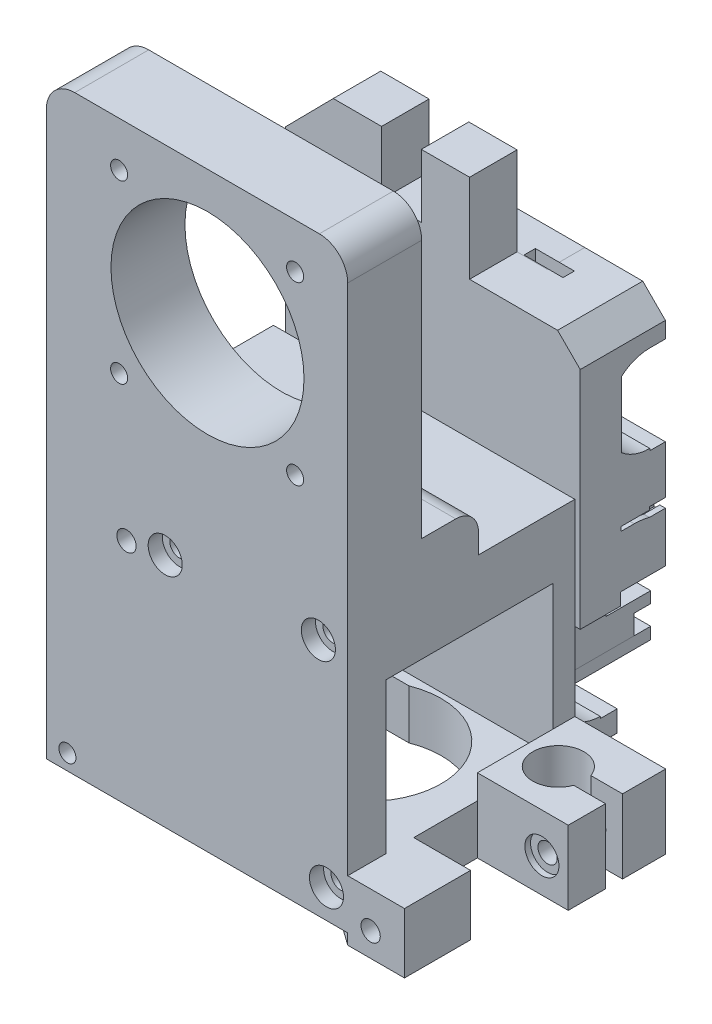
SolidWorks part; units mm, degrees
ref_plane "Front Plane" through (0, 0, 0) normal (0, 0, 1) x (1, 0, 0)
ref_plane "Top Plane" through (0, 0, 0) normal (0, 1, 0) x (1, 0, 0)
ref_plane "Right Plane" through (0, 0, 0) normal (1, 0, 0) x (0, 0, -1)
sketch "Sketch1" plane through (0, 0, 0) normal (0, 0, 1) x (1, 0, 0)
  line L1 (-22.5, 22.5) -> (22.5, 22.5)
  line L2 (-22.5, 22.5) -> (-22.5, -22.5)
  line L3 (-22.5, -22.5) -> (22.5, -22.5)
  line L4 (22.5, 22.5) -> (22.5, -22.5)
  line L5 (-22.5, 22.5) -> (22.5, -22.5) construction
  line L6 (-22.5, -22.5) -> (22.5, 22.5) construction
  point P0 (0, 0)
  dimension "D1" = 45
  dimension "D2" = 45
extrude "Boss-Extrude1" add sketch "Sketch1" along normal blind 35
sketch "Sketch2" plane through (0, 0, 35) normal (0, 0, 1) x (1, 0, 0)
  circle A0 centre (0, 0) radius 13
extrude "Cut-Extrude3" cut sketch "Sketch2" against normal blind 35
sketch "Sketch4" plane through (0, 0, 0) normal (0, 0, -1) x (-1, 0, 0)
  circle A0 centre (-15.8089, 15.9288) radius 1.7
sketch "Sketch5" plane through (0, 0, 0) normal (0, 0, -1) x (-1, 0, 0)
  circle A0 centre (-15.7813, -15.0653) radius 1.7
sketch "Sketch6" plane through (0, 0, 0) normal (0, 0, -1) x (-1, 0, 0)
  circle A0 centre (15.2203, -15.0657) radius 1.7
sketch "Sketch7" plane through (0, 0, 0) normal (0, 0, -1) x (-1, 0, 0)
  circle A0 centre (15.2, 15.9234) radius 1.7
extrude "Cut-Extrude8" cut sketch "Sketch4" against normal blind 35 contours A0
extrude "Cut-Extrude9" cut sketch "Sketch7" against normal blind 35 contours A0
extrude "Cut-Extrude10" cut sketch "Sketch6" against normal blind 35 contours A0
extrude "Cut-Extrude11" cut sketch "Sketch5" against normal blind 35 contours A0
sketch "Sketch8" plane through (22.5, 0, 0) normal (1, 0, 0) x (0, 0, -1)
  line L0 (-4.3639, -12.0361) -> (-35, -12.0361)
  line L2 (-35, -22.5) -> (-35, 22.5) construction
  line L3 (-35, -12.0361) -> (-35, 22.5)
  line L4 (-35, 22.5) -> (-8.4231, 22.5)
  line L5 (-35, 22.5) -> (0, 22.5) construction
  line L6 (-8.4231, 22.5) -> (-8.4231, 12.9255)
  line L7 (-8.4231, 12.9255) -> (-4.3639, 12.9255)
  line L8 (-4.3639, 12.9255) -> (-4.3639, -12.0361)
extrude "Cut-Extrude12" cut sketch "Sketch8" against normal blind 12
sketch "Sketch14" plane through (0, 22.5, 0) normal (0, 1, 0) x (1, 0, 0)
  line L1 (3.1909, -14.7293) -> (9.1909, -14.7293)
  line L2 (3.1909, -14.7293) -> (3.1909, -20.7293)
  line L3 (3.1909, -20.7293) -> (9.1909, -20.7293)
  line L4 (9.1909, -14.7293) -> (9.1909, -20.7293)
  line L5 (3.1909, -14.7293) -> (9.1909, -20.7293) construction
  line L6 (3.1909, -20.7293) -> (9.1909, -14.7293) construction
  point P0 (6.1909, -17.7293)
  point P5 (0, 0)
extrude "Boss-Extrude4" add sketch "Sketch14" along normal blind 2 and the other way blind 37.5
sketch "Sketch20" plane through (0, 24.5, 0) normal (0, 1, 0) x (1, 0, 0)
  line L0 (3.1909, -20.7293) -> (9.1909, -14.7293) construction
  circle A0 centre (6.1909, -17.7293) radius 2.2
  dimension "D1" = 4.4
extrude "Cut-Extrude17" cut sketch "Sketch20" against normal blind 7 and the other way through all contours A0
sketch "Sketch21" plane through (0, 17.5, 0) normal (0, 1, 0) x (1, 0, 0)
  circle A0 centre (6.1909, -17.7293) radius 1.75
extrude "Cut-Extrude18" cut sketch "Sketch21" against normal blind 2
ref_plane "Plane6" through (0, 16.5, 0) normal (0, 1, 0) x (1, 0, 0)
mirror "Mirror6" about plane through (0, 16.5, 0) normal (0, 1, 0) of "Cut-Extrude17"
sketch "Sketch22" plane through (0, -22.5, 0) normal (0, -1, 0) x (1, 0, 0)
  line L1 (-28.0826, 40.0025) -> (25, 40.0025)
  line L2 (-28.0826, 40.0025) -> (-28.0826, 0)
  line L3 (-28.0826, 0) -> (25, 0)
  line L4 (25, 40.0025) -> (25, 0)
  line L5 (-28.0826, 40.0025) -> (25, 0) construction
  line L6 (-28.0826, 0) -> (25, 40.0025) construction
  point P0 (-1.5413, 20.0013)
extrude "Boss-Extrude5" add sketch "Sketch22" along normal blind 44.5712 and the other way blind 1.5626
sketch "Sketch23" plane through (-28.0826, 0, 0) normal (-1, 0, 0) x (0, 0, 1)
  line L1 (3.8043, -58.359) -> (33.254, -58.359)
  line L2 (3.8043, -58.359) -> (3.8043, -31.8415)
  line L3 (3.8043, -31.8415) -> (33.254, -31.8415)
  line L4 (33.254, -58.359) -> (33.254, -31.8415)
  line L5 (3.8043, -58.359) -> (33.254, -31.8415) construction
  line L6 (3.8043, -31.8415) -> (33.254, -58.359) construction
  point P0 (18.5291, -45.1003)
extrude "Cut-Extrude19" cut sketch "Sketch23" against normal through all
sketch "Sketch25" plane through (0, -20.9374, 0) normal (0, 1, 0) x (1, 0, 0)
  circle A0 centre (6.1909, -17.7293) radius 5
extrude "Cut-Extrude24" cut sketch "Sketch25" against normal blind 2.6
sketch "Sketch26" plane through (0, -23.5374, 0) normal (0, 1, 0) x (1, 0, 0)
  circle A0 centre (6.1909, -17.7293) radius 8.1
extrude "Cut-Extrude25" cut sketch "Sketch26" against normal blind 4 contours A0
sketch "Sketch27" plane through (0, -27.5374, 0) normal (0, 1, 0) x (1, 0, 0)
  circle A0 centre (6.1909, -17.7293) radius 6.7
extrude "Cut-Extrude28" cut sketch "Sketch27" against normal blind 6
sketch "Sketch30" plane through (0, -58.359, 0) normal (0, 1, 0) x (1, 0, 0)
  circle A0 centre (6.2079, -17.7293) radius 13
extrude "Cut-Extrude30" cut sketch "Sketch30" against normal blind 10.7676
sketch "Sketch31" plane through (0, -67.0712, 0) normal (0, -1, 0) x (1, 0, 0)
  line L1 (-17.2669, 29.2843) -> (2.0826, 29.2843)
  line L2 (-17.2669, 29.2843) -> (-17.2669, 5.6402)
  line L3 (-17.2669, 5.6402) -> (2.0826, 5.6402)
  line L4 (2.0826, 29.2843) -> (2.0826, 5.6402)
  line L5 (-17.2669, 29.2843) -> (2.0826, 5.6402) construction
  line L6 (-17.2669, 5.6402) -> (2.0826, 29.2843) construction
  point P0 (-7.5922, 17.4622)
extrude "Cut-Extrude31" cut sketch "Sketch31" against normal blind 9.6643
sketch "Sketch34" plane through (-28.0826, 0, 0) normal (-1, 0, 0) x (0, 0, 1)
  circle A4 centre (35.5309, -28.495) radius 1.5
  circle A5 centre (3.5309, -28.495) radius 1.5
  circle A6 centre (35.5309, -60.495) radius 1.5
  circle A7 centre (3.5309, -60.495) radius 1.5
extrude "Cut-Extrude32" cut sketch "Sketch34" against normal blind 9 contours A5 | A7 | A6 | A4
sketch "Sketch37" plane through (25, 0, 0) normal (1, 0, 0) x (0, 0, -1)
  line L1 (-28.3675, -68.9589) -> (-40.0025, -68.9589)
  line L2 (-28.3675, -68.9589) -> (-28.3675, -58.359)
  line L3 (-28.3675, -58.359) -> (-40.0025, -58.359)
  line L4 (-40.0025, -68.9589) -> (-40.0025, -58.359)
  line L5 (-28.3675, -68.9589) -> (-40.0025, -58.359) construction
  line L6 (-28.3675, -58.359) -> (-40.0025, -68.9589) construction
  point P0 (-34.185, -63.659)
extrude "Boss-Extrude6" add sketch "Sketch37" along normal blind 10 and the other way blind 5 draft 29
sketch "Sketch38" plane through (0, 0, 40.0025) normal (0, 0, 1) x (1, 0, 0)
  circle A0 centre (29.0349, -64.7484) radius 1.7
extrude "Cut-Extrude33" cut sketch "Sketch38" against normal blind 10 contours A0
sketch "Sketch39" plane through (0, 0, 40.0025) normal (0, 0, 1) x (1, 0, 0)
  circle A0 centre (-13.9651, -26.7484) radius 1.7
extrude "Cut-Extrude34" cut sketch "Sketch39" against normal through all contours A0
sketch "Sketch40" plane through (25, 0, 0) normal (1, 0, 0) x (0, 0, -1)
  line L0 (0, -67.0712) -> (-28.3675, -67.0712) construction
  line L1 (-17.1599, -54.0712) -> (0, -54.0712)
  line L2 (-17.1599, -54.0712) -> (-17.1599, -67.0712)
  line L3 (-17.1599, -67.0712) -> (0, -67.0712)
  line L4 (0, -54.0712) -> (0, -67.0712)
  line L5 (-17.1599, -54.0712) -> (0, -67.0712) construction
  line L6 (-17.1599, -67.0712) -> (0, -54.0712) construction
  point P0 (-8.5799, -60.5712)
extrude "Boss-Extrude7" add sketch "Sketch40" along normal blind 16 contours L2 L3 L4 L1
sketch "Sketch41" plane through (0, -54.0712, 1.2693) normal (0, 1, 0) x (1, 0, 0)
  circle A0 centre (31.1639, -7.7934) radius 4.5
extrude "Cut-Extrude35" cut sketch "Sketch41" against normal blind 15 contours A0
sketch "Sketch42" plane through (0, -54.0712, 0) normal (0, 1, 0) x (1, 0, 0)
  line L1 (33.5282, -7.5957) -> (42.8596, -7.5957)
  line L2 (33.5282, -7.5957) -> (33.5282, -10.5957)
  line L3 (33.5282, -10.5957) -> (42.8596, -10.5957)
  line L4 (42.8596, -7.5957) -> (42.8596, -10.5957)
  line L5 (33.5282, -7.5957) -> (42.8596, -10.5957) construction
  line L6 (33.5282, -10.5957) -> (42.8596, -7.5957) construction
  point P0 (38.1939, -9.0957)
extrude "Cut-Extrude36" cut sketch "Sketch42" against normal blind 15
sketch "Sketch43" plane through (0, 0, 0) normal (0, 0, -1) x (-1, 0, 0)
  line L1 (-34.6289, -64.4039) -> (-32.7385, -61.0954)
  line L2 (-32.7385, -61.0954) -> (-34.6585, -57.804)
  line L3 (-34.6585, -57.804) -> (-38.4689, -57.821)
  line L4 (-38.4689, -57.821) -> (-40.3594, -61.1295)
  line L5 (-40.3594, -61.1295) -> (-38.4394, -64.421)
  line L6 (-38.4394, -64.421) -> (-34.6289, -64.4039)
  circle A1 centre (-36.5489, -61.1125) radius 3.3 construction
extrude "Cut-Extrude37" cut sketch "Sketch43" against normal blind 5
sketch "Sketch44" plane through (0, 0, 17.1599) normal (0, 0, 1) x (1, 0, 0)
  circle A0 centre (36.3605, -61.0871) radius 1.7
extrude "Cut-Extrude38" cut sketch "Sketch44" against normal blind 23 contours A0
sketch "Sketch48" plane through (0, 0, 0) normal (0, 0, -1) x (-1, 0, 0)
  line L1 (9.0667, -28.8111) -> (10.9572, -25.5026)
  line L2 (10.9572, -25.5026) -> (9.0372, -22.2111)
  line L3 (9.0372, -22.2111) -> (5.2267, -22.2282)
  line L4 (5.2267, -22.2282) -> (3.3362, -25.5367)
  line L5 (3.3362, -25.5367) -> (5.2563, -28.8281)
  line L6 (5.2563, -28.8281) -> (9.0667, -28.8111)
  circle A1 centre (7.1467, -25.5196) radius 3.3 construction
sketch "Sketch49" plane through (0, 0, 0) normal (0, 0, -1) x (-1, 0, 0)
  line L1 (-19.3395, -65.2659) -> (-17.449, -61.9575)
  line L2 (-17.449, -61.9575) -> (-19.369, -58.666)
  line L3 (-19.369, -58.666) -> (-23.1795, -58.6831)
  line L4 (-23.1795, -58.6831) -> (-25.07, -61.9916)
  line L5 (-25.07, -61.9916) -> (-23.15, -65.283)
  line L6 (-23.15, -65.283) -> (-19.3395, -65.2659)
  circle A1 centre (-21.2595, -61.9745) radius 3.3 construction
sketch "Sketch50" plane through (0, 0, 0) normal (0, 0, -1) x (-1, 0, 0)
  line L1 (-17.9116, -28.2435) -> (-16.0212, -24.935)
  line L2 (-16.0212, -24.935) -> (-17.9412, -21.6436)
  line L3 (-17.9412, -21.6436) -> (-21.7517, -21.6606)
  line L4 (-21.7517, -21.6606) -> (-23.6421, -24.9691)
  line L5 (-23.6421, -24.9691) -> (-21.7221, -28.2606)
  line L6 (-21.7221, -28.2606) -> (-17.9116, -28.2435)
  circle A1 centre (-19.8316, -24.9521) radius 3.3 construction
sketch "Sketch51" plane through (0, 0, 40.0025) normal (0, 0, 1) x (1, 0, 0)
  circle A0 centre (-7.1467, -25.5196) radius 1.7
sketch "Sketch52" plane through (0, 0, 40.0025) normal (0, 0, 1) x (1, 0, 0)
  circle A0 centre (19.8316, -24.9521) radius 1.7
sketch "Sketch53" plane through (0, 0, 40.0025) normal (0, 0, 1) x (1, 0, 0)
  circle A0 centre (21.2595, -61.9745) radius 1.7
extrude "Cut-Extrude39" cut sketch "Sketch48" against normal blind 5
extrude "Cut-Extrude40" cut sketch "Sketch49" against normal blind 5
extrude "Cut-Extrude41" cut sketch "Sketch50" against normal blind 5
extrude "Cut-Extrude42" cut sketch "Sketch53" against normal through all contours A0
extrude "Cut-Extrude43" cut sketch "Sketch52" against normal through all contours A0
extrude "Cut-Extrude44" cut sketch "Sketch51" against normal through all
sketch "Sketch55" plane through (0, 0, 0) normal (0, 0, -1) x (-1, 0, 0)
  line L1 (16.7453, -30.1645) -> (18.3136, -26.0487)
  line L2 (18.3136, -26.0487) -> (15.5334, -22.6326)
  line L3 (15.5334, -22.6326) -> (11.1849, -23.3323)
  line L4 (11.1849, -23.3323) -> (9.6166, -27.448)
  line L5 (9.6166, -27.448) -> (12.3967, -30.8642)
  line L6 (12.3967, -30.8642) -> (16.7453, -30.1645)
  circle A0 centre (13.9651, -26.7484) radius 3.8144 construction
extrude "Cut-Extrude46" cut sketch "Sketch55" against normal blind 5
sketch "Sketch57" plane through (0, 0, 40.0025) normal (0, 0, 1) x (1, 0, 0)
  circle A0 centre (-7.1467, -25.5196) radius 3
sketch "Sketch58" plane through (0, 0, 40.0025) normal (0, 0, 1) x (1, 0, 0)
  circle A0 centre (19.8316, -24.9521) radius 3
sketch "Sketch59" plane through (0, 0, 40.0025) normal (0, 0, 1) x (1, 0, 0)
  circle A0 centre (21.2595, -61.9745) radius 3
extrude "Cut-Extrude48" cut sketch "Sketch57" against normal blind 2.5
extrude "Cut-Extrude49" cut sketch "Sketch58" against normal blind 2.5 contours A0
extrude "Cut-Extrude50" cut sketch "Sketch59" against normal blind 2.5 contours A0
sketch "Sketch60" plane through (0, 0, 0) normal (0, 0, -1) x (-1, 0, 0)
  circle A0 centre (-15.8089, 15.9288) radius 3
  circle A1 centre (15.2, 15.9234) radius 3
  circle A2 centre (-15.7813, -15.0653) radius 3
  circle A3 centre (15.2203, -15.0657) radius 3
extrude "Cut-Extrude51" cut sketch "Sketch60" against normal blind 1
sketch "Sketch61" plane through (9.1909, 0, 0) normal (1, 0, 0) x (0, 0, -1)
  line L1 (-21.0836, 7.2178) -> (-14.5415, 7.2178)
  line L2 (-21.0836, 7.2178) -> (-21.0836, -6.8125)
  line L3 (-21.0836, -6.8125) -> (-14.5415, -6.8125)
  line L4 (-14.5415, 7.2178) -> (-14.5415, -6.8125)
  line L5 (-21.0836, 7.2178) -> (-14.5415, -6.8125) construction
  line L6 (-21.0836, -6.8125) -> (-14.5415, 7.2178) construction
  point P0 (-17.8126, 0.2026)
extrude "Cut-Extrude52" cut sketch "Sketch61" against normal blind 6.5 contours L3 L4 L1 L2
sketch "Sketch62" plane through (-22.5, 0, 0) normal (-1, 0, 0) x (0, 0, 1)
  circle A0 centre (9.4038, -7.1271) radius 1.7
sketch "Sketch63" plane through (-22.5, 0, 0) normal (-1, 0, 0) x (0, 0, 1)
  circle A0 centre (29.5162, -7.0688) radius 1.7
sketch "Sketch67" plane through (-22.5, -2.4684, 0) normal (-1, 0, 0) x (0, 0, 1)
  line L1 (26.7141, -1.4425) -> (32.3183, -1.4425)
  line L2 (26.7141, -1.4425) -> (26.7141, -10.4391)
  line L3 (26.7141, -10.4391) -> (32.3183, -10.4391)
  line L4 (32.3183, -1.4425) -> (32.3183, -10.4391)
  line L5 (26.7141, -1.4425) -> (32.3183, -10.4391) construction
  line L6 (26.7141, -10.4391) -> (32.3183, -1.4425) construction
  point P0 (29.5162, -5.9408)
extrude "Boss-Extrude8" add sketch "Sketch67" against normal blind 33
sketch "Sketch68" plane through (-22.5, -2.4684, 0) normal (-1, 0, 0) x (0, 0, 1)
  line L1 (6.6705, -1.2663) -> (12.2748, -1.2663)
  line L2 (6.6705, -1.2663) -> (6.6705, -10.6664)
  line L3 (6.6705, -10.6664) -> (12.2748, -10.6664)
  line L4 (12.2748, -1.2663) -> (12.2748, -10.6664)
  line L5 (6.6705, -1.2663) -> (12.2748, -10.6664) construction
  line L6 (6.6705, -10.6664) -> (12.2748, -1.2663) construction
  point P0 (9.4726, -5.9663)
extrude "Boss-Extrude9" add sketch "Sketch68" against normal blind 33
extrude "Cut-Extrude55" cut sketch "Sketch63" against normal through all contours A0
extrude "Cut-Extrude56" cut sketch "Sketch62" against normal through all contours A0
sketch "Sketch69" plane through (-22.5, 0, 0) normal (-1, 0, 0) x (0, 0, 1)
  circle A0 centre (9.4038, -7.1271) radius 3
  circle A1 centre (29.5162, -7.0688) radius 3
extrude "Cut-Extrude57" cut sketch "Sketch69" against normal blind 2.5
sketch "Sketch70" plane through (0, 0, 28.3675) normal (0, 0, -1) x (-1, 0, 0)
  line L1 (-25.0573, -66.8115) -> (-25.2594, -62.3352)
  line L2 (-25.2594, -62.3352) -> (-29.2371, -60.2722)
  line L3 (-29.2371, -60.2722) -> (-33.0125, -62.6853)
  line L4 (-33.0125, -62.6853) -> (-32.8104, -67.1616)
  line L5 (-32.8104, -67.1616) -> (-28.8328, -69.2246)
  line L6 (-28.8328, -69.2246) -> (-25.0573, -66.8115)
  circle A0 centre (-29.0349, -64.7484) radius 3.8805 construction
extrude "Cut-Extrude58" cut sketch "Sketch70" against normal blind 2.5
sketch "Sketch71" plane through (0, 0, 17.1599) normal (0, 0, 1) x (1, 0, 0)
  circle A0 centre (36.3605, -61.0871) radius 3
extrude "Cut-Extrude59" cut sketch "Sketch71" against normal blind 1 contours A0
sketch "Sketch73" plane through (0, 0, 40.0025) normal (0, 0, 1) x (1, 0, 0)
  circle A0 centre (-24.3693, -64.3228) radius 1.5
extrude "Cut-Extrude61" cut sketch "Sketch73" against normal blind 5
ref_plane "Plane7" through (0, 0, 17.7293) normal (0, 0, 1) x (1, 0, 0)
ref_plane "Plane8" through (0, -20.9374, 0) normal (0, 1, 0) x (1, 0, 0)
sketch "Sketch78" plane through (0, 0, 17.7293) normal (0, 0, 1) x (1, 0, 0)
  line L0 (25, -20.9374) -> (-28.0826, -20.9374) construction
  line L1 (-33.1226, -20.9374) -> (49.9762, -20.9374)
  line L2 (-33.1226, -20.9374) -> (-33.1226, -72.7681)
  line L3 (-33.1226, -72.7681) -> (49.9762, -72.7681)
  line L4 (49.9762, -20.9374) -> (49.9762, -72.7681)
sketch "Sketch79" plane through (0, -20.9374, 0) normal (0, 1, 0) x (1, 0, 0)
  line L1 (-52.1, -49.3859) -> (43.5589, -49.3859)
  line L2 (-52.1, -49.3859) -> (-52.1, 1.9049)
  line L3 (-52.1, 1.9049) -> (43.5589, 1.9049)
  line L4 (43.5589, -49.3859) -> (43.5589, 1.9049)
extrude "Cut-Extrude62" cut sketch "Sketch79" along normal blind 59 contours L1 L4 L3 L2
sketch "Sketch80" plane through (0, -20.9374, 0) normal (0, 1, 0) x (1, 0, 0)
  line L1 (25, -40.0025) -> (-28.0826, -40.0025)
  line L2 (25, -40.0025) -> (25, -26.9707)
  line L3 (25, -26.9707) -> (-28.0826, -26.9707)
  line L4 (-28.0826, -40.0025) -> (-28.0826, -26.9707)
  line L5 (25, -40.0025) -> (-28.0826, -26.9707) construction
  line L6 (25, -26.9707) -> (-28.0826, -40.0025) construction
  line L7 (25, 0) -> (25, -40.0025) construction
  line L8 (-28.0826, -40.0025) -> (-28.0826, 0) construction
  line L9 (25, -40.0025) -> (-28.0826, -40.0025) construction
  point P0 (-1.5413, -33.4866)
extrude "Boss-Extrude10" add sketch "Sketch80" along normal blind 58
fillet "Fillet1" radius 5 2 edges at (-28.0826, 37.0626, 33.4866) (25, 37.0626, 33.4866)
sketch "Sketch84" plane through (0, 0, 26.9707) normal (0, 0, -1) x (-1, 0, 0)
  circle A0 centre (-0.299, 13.6036) radius 17
extrude "Cut-Extrude63" cut sketch "Sketch84" against normal blind 22
sketch "Sketch85" plane through (0, 0, 40.0025) normal (0, 0, 1) x (1, 0, 0)
  circle A0 centre (15.7368, 29.1356) radius 1.5
  circle A1 centre (15.7368, -1.8644) radius 1.5
  circle A2 centre (-15.2632, -1.8644) radius 1.5
  circle A3 centre (-15.2632, 29.1356) radius 1.5
extrude "Cut-Extrude64" cut sketch "Sketch85" against normal blind 15
sketch "Sketch86" plane through (0, -20.9374, 0) normal (0, 1, 0) x (1, 0, 0)
  line L0 (25, -26.9707) -> (-28.0826, -26.9707) construction
  line L1 (-28.0826, -26.9707) -> (-14.3865, -26.9707)
  line L2 (-28.0826, -26.9707) -> (-28.0826, -16.9707)
  line L3 (-28.0826, -16.9707) -> (-14.3865, -16.9707)
  line L4 (-14.3865, -26.9707) -> (-14.3865, -16.9707)
extrude "Boss-Extrude11" add sketch "Sketch86" along normal blind 7.5
fillet "Fillet3" radius 3 1 edges at (-21.2346, -13.4374, 16.9707)
sketch "Sketch87" plane through (0, -20.9374, 0) normal (0, 1, 0) x (1, 0, 0)
  line L0 (25, -26.9707) -> (-14.3865, -26.9707) construction
  line L1 (25, -16.9707) -> (14.2343, -16.9707)
  line L2 (25, -16.9707) -> (25, -26.9707)
  line L3 (25, -26.9707) -> (14.2343, -26.9707)
  line L4 (14.2343, -16.9707) -> (14.2343, -26.9707)
  line L5 (-14.3865, -16.9707) -> (-28.0826, -16.9707) construction
  line L6 (25, 0) -> (25, -26.9707) construction
extrude "Boss-Extrude12" add sketch "Sketch87" along normal blind 7.5
sketch "Sketch89" plane through (0, -20.9374, 0) normal (0, 1, 0) x (1, 0, 0)
  line L1 (61.8406, -52.5891) -> (-70.6943, -52.5891)
  line L2 (61.8406, -52.5891) -> (61.8406, 20.0544)
  line L3 (61.8406, 20.0544) -> (-70.6943, 20.0544)
  line L4 (-70.6943, -52.5891) -> (-70.6943, 20.0544)
fillet "Fillet6" radius 4 1 edges at (19.6171, -13.4374, 16.9707)
sketch "Sketch90" plane through (0, 0, 0) normal (0, 0, -1) x (-1, 0, 0)
  line L0 (17.0373, -68.362) -> (17.0373, -50.6891)
  line L1 (14.2497, -71.1901) -> (-14.1775, -71.1901)
  line L2 (25.9937, -36.474) -> (25.9937, 10.3734)
  line L4 (-25.9551, -36.6603) -> (-25.9551, -0.6679)
  line L5 (17.0373, -50.6891) -> (26.0173, -50.6891)
  line L6 (-17.4627, -50.6803) -> (-17.4627, -67.8636)
  line L7 (-17.4627, -50.6803) -> (-23.3678, -50.6803)
  line L8 (-17.4627, -67.8636) -> (-14.1775, -71.1901)
  line L9 (17.0373, -68.362) -> (14.2497, -71.1901)
  line L10 (-23.3678, -50.6803) -> (-23.3627, -48.6193)
  line L11 (-23.3627, -43.1803) -> (-23.3627, -48.6193)
  line L13 (26.0173, -50.6891) -> (26.0173, -40.6819)
  line L14 (26.0173, -40.6819) -> (25.9937, -36.474)
  line L15 (-25.9551, -0.6679) -> (-21.9627, 3.3244)
  line L16 (-21.9627, 3.3244) -> (-6.4627, 3.3557)
  line L17 (-6.4627, 3.3557) -> (-6.4627, 18.9227)
  line L18 (-23.3627, -43.1803) -> (-23.3627, -40.3081)
  line L19 (17.549, 18.9227) -> (25.9937, 10.3734)
  line L20 (2.0414, 18.9227) -> (2.0108, 7.7806)
  line L21 (9.0396, 7.7806) -> (9.0396, 18.9227)
  line L22 (2.0108, 7.7806) -> (9.0396, 7.7806)
  line L23 (2.0414, 18.9227) -> (-6.4627, 18.9227)
  line L24 (9.0396, 18.9227) -> (17.549, 18.9227)
  line L25 (-25.9551, -36.6603) -> (-25.9551, -40.3081)
  line L26 (-25.9551, -40.3081) -> (-23.3627, -40.3081)
extrude "Boss-Extrude13" add sketch "Sketch90" along normal blind 15
ref_plane "Plane9" through (24.9551, 0, 0) normal (1, 0, 0) x (0, 0, -1)
sketch "Sketch93" plane through (24.9551, 0, 0) normal (1, 0, 0) x (0, 0, -1)
  circle A0 centre (12.2562, -11.1714) radius 7.6272
  point P2 (12.3899, -11.1491)
  point P3 (12.2562, -11.1714)
extrude "Cut-Extrude66" cut sketch "Sketch93" against normal blind 49.5
sketch "Sketch94" plane through (25.9551, 0, 0) normal (1, 0, 0) x (0, 0, -1)
  line L0 (7.3045, -5.318) -> (7.3045, -17.0156)
  line L1 (12.2545, -3.5044) -> (16.3704, -3.5044)
  line L2 (16.3704, -4.7037) -> (16.3704, -3.5044)
  line L3 (12.2545, -18.8291) -> (12.2475, -19.1753)
  line L4 (12.2475, -19.1753) -> (15.2475, -19.1908)
  line L5 (15.2475, -19.1908) -> (15.2475, -18.2204)
  arc A0 (7.3045, -17.0156) -> (12.2545, -18.8291) centre (12.2545, -11.1668) ccw
  arc A1 (12.2545, -3.5044) -> (7.3045, -5.318) centre (12.2545, -11.1668) ccw
  arc A2 (15.2475, -18.2204) -> (16.3704, -4.7037) centre (12.2545, -11.1668) ccw
extrude "Cut-Extrude67" cut sketch "Sketch94" against normal blind 53.5
ref_plane "Plane10" through (12.4627, 0, 0) normal (1, 0, 0) x (0, 0, -1)
sketch "Sketch95" plane through (12.4627, 0, 0) normal (1, 0, 0) x (0, 0, -1)
  circle A0 centre (12.0924, -56.1751) radius 7.6764
  point P2 (12.8802, -56.0146)
  point P3 (12.4047, -56.2159)
  point P4 (12.8001, -56.3056)
  point P5 (12.4856, -56.2898)
  point P6 (11.8974, -56.2772)
  point P7 (12.0924, -56.1751)
extrude "Cut-Extrude68" cut sketch "Sketch95" against normal blind 25.2
sketch "Sketch96" plane through (17.4627, 0, 0) normal (1, 0, 0) x (0, 0, -1)
  line L0 (7.0266, -61.9445) -> (7.0939, -50.6803)
  line L1 (7.0939, -50.6803) -> (18.0396, -50.6803)
  line L3 (12.0174, -63.8278) -> (12.0174, -64.1642)
  line L4 (12.0174, -64.1642) -> (15, -64.1642)
  line L5 (15, -50.6803) -> (15, -67.8636) construction
  line L6 (15, -64.1642) -> (15, -63.2948)
  arc A0 (7.0266, -61.9445) -> (12.0174, -63.8278) centre (12.1456, -55.9335) ccw
  arc A1 (15, -63.2948) -> (18.0396, -50.6803) centre (12.1456, -55.9335) ccw
  point P6 (15, -63.2948)
extrude "Cut-Extrude69" cut sketch "Sketch96" against normal blind 34.5
sketch "Sketch98" plane through (23.3627, 0, 0) normal (1, 0, 0) x (0, 0, -1)
  line L1 (7.1104, -43.1905) -> (15.1235, -43.1905)
  line L2 (7.1104, -43.1905) -> (7.1104, -38.1356)
  line L3 (7.1104, -38.1356) -> (15.1235, -38.1356)
  line L4 (15.1235, -43.1905) -> (15.1235, -38.1356)
  point P4 (7.1558, -36.6135)
  point P5 (7.1104, -38.1356)
  point P6 (15.1235, -43.1905)
extrude "Cut-Extrude70" cut sketch "Sketch98" against normal through all both and the other way through all
sketch "Sketch99" plane through (23.3627, 0, 0) normal (1, 0, 0) x (0, 0, -1)
  line L1 (15, -48.6193) -> (12.1018, -48.6193)
  line L2 (15, -48.6193) -> (15, -45.1749)
  line L3 (15, -45.1749) -> (12.1018, -45.1749)
  line L4 (12.1018, -48.6193) -> (12.1018, -45.1749)
extrude "Cut-Extrude71" cut sketch "Sketch99" against normal blind 49.5
sketch "Sketch100" plane through (0, 0, -15) normal (0, 0, -1) x (-1, 0, 0)
  line L0 (-25.9551, -28.9452) -> (-24.9628, -28.9452)
  line L1 (-25.9551, -19.1895) -> (-25.9551, -38.1356) construction
  line L2 (-24.9628, -28.9452) -> (-24.9628, -29.6536)
  line L3 (-24.9628, -29.6536) -> (-23.9626, -29.6536)
  line L4 (-23.9626, -29.6536) -> (-23.9626, -28.9452)
  line L5 (-23.9626, -28.9452) -> (-22.9642, -28.9452)
  line L6 (-22.9642, -28.9452) -> (-22.9586, -29.6536)
  line L7 (-22.9586, -29.6536) -> (-21.963, -29.6536)
  line L8 (-21.963, -29.6536) -> (-21.963, -28.9452)
  line L9 (-21.963, -28.9452) -> (-20.9649, -28.9452)
  line L10 (-20.9649, -28.9452) -> (-20.9593, -29.6526)
  line L11 (-20.9593, -29.6526) -> (-19.966, -29.6447)
  line L12 (-19.966, -29.6447) -> (-19.9723, -28.852)
  line L13 (-19.9723, -28.852) -> (-19.3112, -28.5436)
  line L14 (-19.3112, -28.5436) -> (-19.0086, -29.1925)
  line L15 (-19.0086, -29.1925) -> (-18.1014, -28.7694)
  line L16 (-18.1014, -28.7694) -> (-18.4041, -28.1205)
  line L17 (-18.4041, -28.1205) -> (-17.5043, -27.7008)
  line L18 (-17.5043, -27.7008) -> (-17.2016, -28.3497)
  line L19 (-17.2016, -28.3497) -> (-16.2902, -27.9246)
  line L20 (-16.2902, -27.9246) -> (-16.5928, -27.2757)
  line L21 (-16.5928, -27.2757) -> (-15.6945, -26.8567)
  line L22 (-15.6945, -26.8567) -> (-15.2198, -27.8743)
  line L23 (-15.2198, -27.8743) -> (-14.3102, -27.4501)
  line L24 (-14.3102, -27.4501) -> (-14.7283, -26.5536)
  line L25 (-14.7283, -26.5536) -> (-13.7535, -26.5536)
  line L26 (-13.7535, -26.5536) -> (-13.7535, -27.2739)
  line L27 (-13.7535, -27.2739) -> (-12.7588, -27.2739)
  line L28 (-12.7588, -27.2739) -> (-12.7588, -26.5536)
  line L29 (-12.7588, -26.5536) -> (-11.7545, -26.5536)
  line L30 (-11.7545, -26.5536) -> (-11.7545, -27.2739)
  line L31 (-11.7545, -27.2739) -> (-10.7569, -27.2739)
  line L32 (-10.7569, -27.2739) -> (-10.7569, -26.5536)
  line L33 (-10.7569, -26.5536) -> (-9.7531, -26.5536)
  line L34 (-9.7531, -26.5536) -> (-9.7531, -27.2739)
  line L35 (-9.7531, -27.2739) -> (-8.7561, -27.2739)
  line L36 (-8.7561, -27.2739) -> (-8.7561, -26.5536)
  line L37 (-8.7561, -26.5536) -> (-7.7518, -26.5536)
  line L38 (-7.7518, -26.5536) -> (-7.7518, -27.2739)
  line L39 (-7.7518, -27.2739) -> (-7.4588, -27.2739)
  line L40 (-7.4588, -27.2739) -> (-6.7129, -27.7765)
  line L41 (-6.7129, -27.7765) -> (-6.455, -27.9003)
  line L42 (-6.455, -27.9003) -> (-6.8083, -25.7675)
  line L43 (-6.8083, -25.7675) -> (-15.08, -25.7675)
  line L44 (-15.08, -25.7675) -> (-20.1972, -28.16)
  line L45 (-20.1972, -28.16) -> (-25.9551, -28.1993)
  line L46 (-25.9551, -28.1993) -> (-25.9551, -28.9452)
  point P26 (-15.08, -25.7675)
sketch "Sketch104" plane through (0, 0, -15) normal (0, 0, -1) x (-1, 0, 0)
  line L0 (-25.9627, -29.3147) -> (-24.9628, -29.3147)
  line L1 (-24.9628, -28.9452) -> (-24.9628, -29.6536) construction
  line L2 (-24.9628, -29.3147) -> (-24.9627, -30.0666)
  line L3 (-24.9627, -30.0666) -> (-23.9627, -30.0666)
  line L4 (-23.9627, -30.0666) -> (-23.9626, -29.2994)
  line L5 (-23.9626, -29.6536) -> (-23.9626, -28.9452) construction
  line L6 (-23.9626, -29.2994) -> (-22.9614, -29.2994)
  line L7 (-22.9642, -28.9452) -> (-22.9586, -29.6536) construction
  line L8 (-22.9614, -29.2994) -> (-22.9627, -30.0666)
  line L9 (-22.9627, -30.0666) -> (-21.9627, -30.0666)
  line L10 (-21.9627, -30.0666) -> (-21.9627, -29.3147)
  line L11 (-21.9627, -29.3147) -> (-20.9627, -29.3147)
  line L12 (-20.9627, -29.3147) -> (-20.9627, -30.0666)
  line L13 (-20.9627, -30.0666) -> (-19.9627, -30.0666)
  line L14 (-19.9627, -30.0666) -> (-19.9627, -29.3)
  line L15 (-19.9627, -29.3) -> (-19.1441, -28.9183)
  line L16 (-19.1441, -28.9183) -> (-18.8263, -29.5997)
  line L17 (-18.8263, -29.5997) -> (-17.92, -29.1771)
  line L18 (-17.92, -29.1771) -> (-18.2378, -28.4956)
  line L19 (-18.2378, -28.4956) -> (-17.3315, -28.073)
  line L20 (-17.3315, -28.073) -> (-17.0137, -28.7545)
  line L21 (-17.0137, -28.7545) -> (-16.1074, -28.3318)
  line L22 (-16.1074, -28.3318) -> (-16.4252, -27.6504)
  line L23 (-16.4252, -27.6504) -> (-15.5188, -27.2278)
  line L24 (-15.5188, -27.2278) -> (-15.2011, -27.9092)
  line L25 (-15.2011, -27.9092) -> (-14.2948, -27.4866)
  line L26 (-14.2948, -27.4866) -> (-14.5521, -26.9347)
  line L27 (-14.5521, -26.9347) -> (-13.7627, -26.9347)
  line L28 (-13.7627, -26.9347) -> (-13.7627, -27.6866)
  line L29 (-13.7627, -27.6866) -> (-12.7627, -27.6866)
  line L30 (-12.7627, -27.6866) -> (-12.7588, -26.9137)
  line L31 (-12.7588, -27.2739) -> (-12.7588, -26.5536) construction
  line L32 (-12.7588, -26.9137) -> (-11.7627, -26.9347)
  line L33 (-11.7627, -26.9347) -> (-11.7627, -27.6866)
  line L34 (-11.7627, -27.6866) -> (-10.7627, -27.6866)
  line L35 (-10.7627, -27.6866) -> (-10.7627, -26.9347)
  line L36 (-10.7627, -26.9347) -> (-9.7627, -26.9347)
  line L37 (-9.7627, -26.9347) -> (-9.7627, -27.6866)
  line L38 (-9.7627, -27.6866) -> (-8.7627, -27.6866)
  line L39 (-8.7627, -27.6866) -> (-8.7627, -26.9347)
  line L40 (-8.7627, -26.9347) -> (-7.7627, -26.9347)
  line L41 (-7.7627, -26.9347) -> (-7.7627, -27.6866)
  line L42 (-7.7627, -27.6866) -> (-6.8547, -27.6866)
  line L43 (-6.8547, -27.6866) -> (-6.8367, -25.2817)
  line L44 (-6.8367, -25.2817) -> (-6.8381, -25.2833)
  line L45 (-6.8381, -25.2833) -> (-15.2958, -25.3392)
  line L46 (-15.2958, -25.3392) -> (-20.3315, -27.6866)
  line L47 (-20.3315, -27.6866) -> (-25.9551, -27.6866)
  line L48 (-25.9551, -19.1895) -> (-25.9551, -38.1356) construction
  line L49 (-25.9551, -27.6866) -> (-25.9627, -29.3147)
  point P56 (-15.2011, -25.3386)
  point P57 (-20.3315, -27.6866)
  point P58 (-25.9551, -27.6866)
extrude "Cut-Extrude75" cut sketch "Sketch104" against normal blind 2.8
extrude "Cut-Extrude76" cut sketch "Sketch100" against normal blind 7.8
ref_plane "Plane11" through (25.9551, -29.3147, -12.2) normal (-1, 0, 0) x (0, 0, 1)
fillet "Fillet9" radius 10 1 edges at (25.4589, -28.9452, -12.2)
sketch "Sketch107" plane through (0, 0, -15) normal (0, 0, -1) x (-1, 0, 0)
  line L0 (8.6873, -27.1166) -> (8.6873, -26.3647)
  line L1 (8.6873, -26.3647) -> (9.6873, -26.3647)
  line L2 (9.6873, -26.3647) -> (9.6873, -27.1166)
  line L3 (9.6873, -27.1166) -> (10.6873, -27.1166)
  line L4 (10.6873, -27.1166) -> (10.6873, -26.3647)
  line L5 (10.6873, -26.3647) -> (11.3006, -26.3647)
  line L6 (11.3006, -26.3647) -> (11.5044, -26.4824)
  line L7 (11.5044, -26.4824) -> (11.1285, -27.1335)
  line L8 (11.1285, -27.1335) -> (11.9945, -27.6335)
  line L9 (11.9945, -27.6335) -> (12.3705, -26.9824)
  line L10 (12.3705, -26.9824) -> (13.2365, -27.4824)
  line L11 (13.2365, -27.4824) -> (12.8606, -28.1335)
  line L12 (12.8606, -28.1335) -> (13.7266, -28.6335)
  line L13 (13.7266, -28.6335) -> (14.1025, -27.9824)
  line L14 (14.1025, -27.9824) -> (14.9685, -28.4824)
  line L15 (14.9685, -28.4824) -> (14.5926, -29.1335)
  line L16 (14.5926, -29.1335) -> (15.4586, -29.6335)
  line L17 (15.4586, -29.6335) -> (15.8346, -28.9824)
  line L18 (15.8346, -28.9824) -> (16.7006, -29.4824)
  line L19 (16.7006, -29.4824) -> (16.3247, -30.1335)
  line L20 (16.3247, -30.1335) -> (17.1907, -30.6335)
  line L21 (17.1907, -30.6335) -> (17.5666, -29.9824)
  line L22 (17.5666, -29.9824) -> (18.4326, -30.4824)
  line L23 (18.4326, -30.4824) -> (18.0567, -31.1335)
  line L24 (18.0567, -31.1335) -> (18.9227, -31.6335)
  line L25 (18.9227, -31.6335) -> (19.2987, -30.9824)
  line L26 (19.2987, -30.9824) -> (20.0373, -31.4088)
  line L27 (20.0373, -31.4088) -> (20.0373, -32.0665)
  line L28 (20.0373, -32.0665) -> (21.0373, -32.0665)
  line L29 (21.0373, -32.0665) -> (21.0373, -31.3147)
  line L30 (21.0373, -31.3147) -> (22.0373, -31.3147)
  line L31 (22.0373, -31.3147) -> (22.0373, -32.0665)
  line L32 (22.0373, -32.0665) -> (23.0373, -32.0665)
  line L33 (23.0373, -32.0665) -> (23.0373, -31.3147)
  line L34 (23.0373, -31.3147) -> (24.0373, -31.3147)
  line L35 (24.0373, -31.3147) -> (24.0373, -32.0665)
  line L36 (24.0373, -32.0665) -> (25.0373, -32.0665)
  line L37 (25.0373, -32.0665) -> (25.0373, -31.3079)
  line L38 (25.0373, -31.3079) -> (26.0373, -31.3147)
  line L39 (26.0373, -31.3147) -> (25.9937, -30.1821)
  line L40 (25.9937, -36.474) -> (25.9937, -19.1895) construction
  line L41 (25.9937, -30.1821) -> (20.1665, -30.1821)
  line L42 (20.1665, -30.1821) -> (11.5852, -25.2668)
  line L43 (11.5852, -25.2668) -> (8.2237, -25.2255)
  line L44 (8.2237, -25.2255) -> (7.9365, -27.1166)
  line L45 (7.9365, -27.1166) -> (8.6873, -27.1166)
sketch "Sketch108" plane through (0, 0, -15) normal (0, 0, -1) x (-1, 0, 0)
  line L0 (8.2264, -26.6999) -> (8.6587, -26.7322)
  line L1 (8.6587, -26.7322) -> (8.6587, -25.9627)
  line L2 (8.6587, -25.9627) -> (9.6644, -25.9627)
  line L3 (9.6644, -25.9627) -> (9.6873, -26.6994)
  line L4 (9.6873, -26.6994) -> (10.6873, -26.6994)
  line L5 (10.6873, -26.6994) -> (10.6873, -25.9627)
  line L6 (10.6873, -25.9627) -> (11.4044, -25.9627)
  line L7 (11.4044, -25.9627) -> (11.7067, -26.1175)
  line L8 (11.7067, -26.1175) -> (11.3604, -26.7935)
  line L9 (11.3604, -26.7935) -> (12.1825, -27.308)
  line L10 (11.9945, -27.6335) -> (12.3705, -26.9824) construction
  line L11 (12.1825, -27.308) -> (12.5588, -26.6562)
  line L12 (12.5588, -26.6562) -> (13.4099, -27.1477)
  line L13 (13.4099, -27.1477) -> (13.0485, -27.808)
  line L14 (13.2365, -27.4824) -> (12.8606, -28.1335) construction
  line L15 (13.0485, -27.808) -> (13.9146, -28.3079)
  line L16 (13.7266, -28.6335) -> (14.1025, -27.9824) construction
  line L17 (13.9146, -28.3079) -> (14.3024, -27.6361)
  line L18 (14.3024, -27.6361) -> (15.1639, -28.1335)
  line L19 (15.1639, -28.1335) -> (14.7806, -28.8079)
  line L20 (14.7806, -28.8079) -> (15.6466, -29.308)
  line L21 (15.4586, -29.6335) -> (15.8346, -28.9824) construction
  line L22 (15.6466, -29.308) -> (16.0379, -28.6302)
  line L23 (16.0379, -28.6302) -> (16.9035, -29.13)
  line L24 (16.9035, -29.13) -> (16.5126, -29.8079)
  line L25 (16.7006, -29.4824) -> (16.3247, -30.1335) construction
  line L26 (16.5126, -29.8079) -> (17.3362, -30.2827)
  line L27 (17.3362, -30.2827) -> (17.7516, -29.6189)
  line L28 (17.7516, -29.6189) -> (18.6251, -30.1225)
  line L29 (18.6251, -30.1225) -> (18.2561, -30.7733)
  line L30 (18.2561, -30.7733) -> (19.1107, -31.2666)
  line L31 (19.1107, -31.2666) -> (19.485, -30.6183)
  line L32 (19.485, -30.6183) -> (20.0465, -30.9425)
  line L33 (20.0465, -30.9425) -> (20.0444, -31.6493)
  line L34 (20.0444, -31.6493) -> (21.0373, -31.6493)
  line L35 (21.0373, -31.6493) -> (21.0373, -30.8966)
  line L36 (21.0373, -30.8966) -> (22.0388, -30.8966)
  line L37 (22.0388, -30.8966) -> (22.0373, -31.6493)
  line L38 (22.0373, -31.3147) -> (22.0373, -32.0665) construction
  line L39 (22.0373, -31.6493) -> (23.0373, -31.6493)
  line L40 (23.0373, -32.0665) -> (23.0373, -31.3147) construction
  line L41 (23.0373, -31.6493) -> (23.0373, -30.8966)
  line L42 (23.0373, -30.8966) -> (24.0311, -30.8966)
  line L43 (24.0311, -30.8966) -> (24.0373, -31.6493)
  line L44 (24.0373, -31.6493) -> (25.0373, -31.6493)
  line L45 (25.0373, -32.0665) -> (25.0373, -31.3079) construction
  line L46 (25.0373, -31.6493) -> (25.0373, -30.8966)
  line L47 (25.0373, -30.8966) -> (26.0373, -30.9121)
  line L48 (26.0373, -30.9121) -> (25.9937, -29.6617)
  line L49 (25.9937, -36.474) -> (25.9937, -19.1895) construction
  line L50 (25.9937, -29.6617) -> (20.0843, -29.6617)
  line L51 (20.0843, -29.6617) -> (11.5106, -24.7117)
  line L52 (11.5106, -24.7117) -> (7.7353, -24.6752)
  line L53 (7.7353, -24.6752) -> (8.2264, -26.6999)
extrude "Cut-Extrude77" cut sketch "Sketch107" against normal blind 2.8
extrude "Cut-Extrude78" cut sketch "Sketch108" against normal blind 7.8
sketch "Sketch109" plane through (0, 0, -15) normal (0, 0, -1) x (-1, 0, 0)
  line L5 (19.305, -0.4593) -> (22.7798, -0.4593)
  line L6 (19.305, -0.4593) -> (19.305, -2.2282)
  line L7 (19.305, -2.2282) -> (22.7798, -2.2282)
  line L8 (22.7798, -0.4593) -> (22.7798, -2.2282)
ref_plane "Plane12" through (-20.9937, 0, 0) normal (-1, 0, 0) x (0, 0, 1)
sketch "Sketch111" plane through (-20.9937, 0, 0) normal (-1, 0, 0) x (0, 0, 1)
  circle A0 centre (-11.5069, -11.1119) radius 9.9738
  point P2 (-10.427, -11.3009)
  point P3 (-11.5069, -11.1119)
sweep "Cut-Sweep2" cut profiles "Sketch109" path "Sketch111"
sketch "Sketch112" plane through (0, 0, -15) normal (0, 0, -1) x (-1, 0, 0)
  line L1 (-20.7374, -0.4219) -> (-17.1806, -0.4219)
  line L2 (-20.7374, -0.4219) -> (-20.7374, -2.2289)
  line L3 (-20.7374, -2.2289) -> (-17.1806, -2.2289)
  line L4 (-17.1806, -0.4219) -> (-17.1806, -2.2289)
ref_plane "Plane13" through (18.9551, 0, 0) normal (1, 0, 0) x (0, 0, -1)
sketch "Sketch113" plane through (18.9551, 0, 0) normal (1, 0, 0) x (0, 0, -1)
  circle A0 centre (13.3305, -11.1949) radius 9.8876
  point P2 (13.0524, -11.3593)
  point P3 (13.1512, -11.089)
  point P4 (13.3305, -11.1949)
sweep "Cut-Sweep3" cut profiles "Sketch112" path "Sketch113"
ref_plane "Plane14" through (0, 0, -9.5) normal (0, 0, -1) x (-1, 0, 0)
sketch "Sketch115" plane through (0, 0, -9.5) normal (0, 0, -1) x (-1, 0, 0)
  line L0 (-14.4186, -0.1631) -> (-14.4186, 4.2277)
  line L4 (-14.4186, -0.1631) -> (-12.7002, -3.1395)
  line L5 (-12.7002, -3.1395) -> (-9.2633, -3.1395)
  line L6 (-9.2633, -3.1395) -> (-7.5449, -0.1631)
  line L10 (9.0279, -0.1631) -> (10.7492, -3.1445)
  line L11 (10.7492, -3.1445) -> (14.1918, -3.1445)
  line L12 (14.1918, -3.1445) -> (15.9131, -0.1631)
  line L13 (-7.5449, -0.1631) -> (-7.5449, 4.6855)
  line L14 (9.0279, -0.1631) -> (9.0279, 4.05)
  line L15 (15.9131, -0.1631) -> (15.9131, 4.3954)
  line L20 (-14.4186, 4.2277) -> (-7.5449, 4.6855)
  line L21 (10.7492, 2.8183) -> (9.8886, 1.3276) [skipped]
  line L22 (15.9131, -0.1631) -> (15.0525, 1.3276) [skipped]
  line L23 (-12.7002, 2.8133) -> (-13.5594, 1.3251) [skipped]
  line L24 (-7.5449, -0.1631) -> (-8.4041, 1.3251) [skipped]
  line L25 (15.9131, 4.3954) -> (9.0279, 4.05)
  line L27 (-9.2633, 2.8133) -> (-10.9817, 2.8133) [skipped]
  line L28 (14.1918, 2.8183) -> (12.4705, 2.8183) [skipped]
  circle A0 centre (-10.9817, -0.1631) radius 2.5 construction
  circle A1 centre (12.4705, -0.1631) radius 2.5 construction
  dimension "D1" = 5
  dimension "D2" = 5
extrude "Cut-Extrude79" cut sketch "Sketch115" against normal mid plane 2
sketch "Sketch116" plane through (-25.9937, 0, 0) normal (-1, 0, 0) x (0, 0, 1)
  line L1 (-8.3638, 3.345) -> (-19.7477, 3.345)
  line L2 (-8.3638, 3.345) -> (-8.3638, 20.7304)
  line L3 (-8.3638, 20.7304) -> (-19.7477, 20.7304)
  line L4 (-19.7477, 3.345) -> (-19.7477, 20.7304)
  point P4 (-19.7477, 20.7304)
extrude "Cut-Extrude80" cut sketch "Sketch116" against normal blind 64
ref_plane "Plane15" through (0, 0, -11.2) normal (0, 0, -1) x (-1, 0, 0)
sketch "Sketch117" plane through (0, 0, -11.2) normal (0, 0, -1) x (-1, 0, 0)
  line L0 (-12.8024, -67.142) -> (-12.8024, -62.5486)
  line L1 (-8.4723, -69.642) -> (-7.0289, -67.142)
  line L5 (-12.8024, -67.142) -> (-11.359, -69.642)
  line L6 (-11.359, -69.642) -> (-8.4723, -69.642)
  line L7 (11.4583, -69.6854) -> (12.9017, -67.1854)
  line L11 (7.1282, -67.1854) -> (8.5716, -69.6854)
  line L12 (8.5716, -69.6854) -> (11.4583, -69.6854)
  line L13 (-7.0289, -67.142) -> (-6.8957, -62.5486)
  line L14 (-12.8024, -62.5486) -> (-6.8957, -62.5486)
  line L15 (7.1282, -67.1854) -> (7.1282, -62.6875)
  line L16 (7.1282, -62.6875) -> (12.9017, -62.6875)
  line L17 (12.9017, -62.6875) -> (12.9017, -67.1854)
  line L19 (8.5716, -64.6854) -> (7.8499, -65.9354) [skipped]
  line L20 (12.9017, -67.1854) -> (12.18, -65.9354) [skipped]
  line L21 (10.015, -64.6854) -> (8.5716, -64.6854) [skipped]
  line L22 (-8.4723, -64.642) -> (-9.9157, -64.642) [skipped]
  line L23 (-7.0289, -67.142) -> (-7.7506, -65.892) [skipped]
  line L24 (-12.0807, -65.892) -> (-12.8024, -67.142) [skipped]
  circle A0 centre (-9.9157, -67.142) radius 2.5 construction
  circle A1 centre (10.015, -67.1854) radius 2.5 construction
  dimension "D1" = 5
  dimension "D2" = 5
extrude "Cut-Extrude81" cut sketch "Sketch117" against normal mid plane 2
